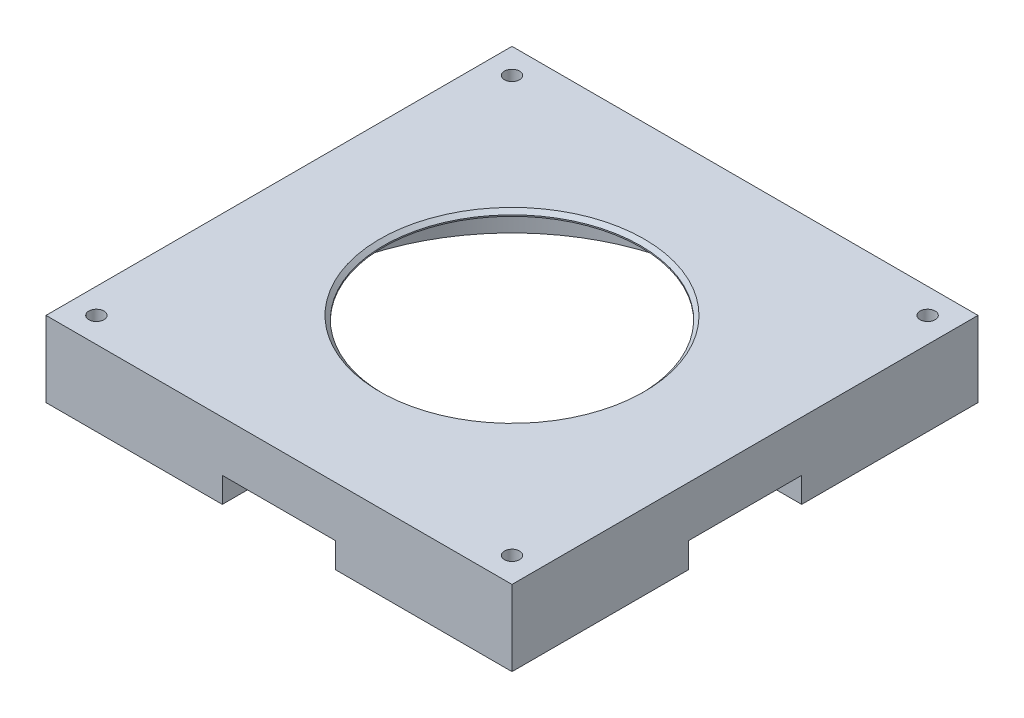
SolidWorks part; units mm, degrees
material "PBT General Purpose"
ref_plane "Front Plane" through (0, 0, 0) normal (0, 0, 1) x (1, 0, 0)
ref_plane "Top Plane" through (0, 0, 0) normal (0, 1, 0) x (1, 0, 0)
ref_plane "Right Plane" through (0, 0, 0) normal (1, 0, 0) x (0, 0, -1)
sketch "Sketch1" plane through (0, 0, 0) normal (0, 0, 1) x (1, 0, 0)
  line L1 (51, -2) -> (82.5, -2)
  line L2 (82.5, -2) -> (82.5, -30)
  line L5 (82.5, -30) -> (85.5, -30)
  line L6 (85.5, -30) -> (85.5, 0)
  line L7 (85.5, 0) -> (51, 0)
  line L8 (51, -2) -> (51, 0)
  line L9 (0, 0) -> (51, 0) construction
  line L10 (0, 0) -> (0, -6.871) construction
  point P2 (65, -8)
  point P3 (64.6623, -8)
  dimension "D1" = 3
  dimension "D3" = 2
  dimension "D5" = 30
  dimension "D6" = 82.5
  dimension "D7" = 51
revolve "Revolve1" add sketch "Sketch1" angle 360 about L10
chamfer "Chamfer1" distance 1.5 angle 45 1 edges at (0, 0, 51)
sketch "Sketch2" plane through (0, -30, 0) normal (0, -1, 0) x (1, 0, 0)
  line L1 (-92.5, -92.5) -> (92.5, -92.5)
  line L2 (-92.5, -92.5) -> (-92.5, 92.5)
  line L3 (-92.5, 92.5) -> (92.5, 92.5)
  line L4 (92.5, -92.5) -> (92.5, 92.5)
  line L5 (-92.5, -92.5) -> (92.5, 92.5) construction
  line L6 (-92.5, 92.5) -> (92.5, -92.5) construction
  line L7 (-82.5, -82.5) -> (82.5, -82.5) construction
  line L8 (-82.5, -82.5) -> (-82.5, 82.5) construction
  line L9 (-82.5, 82.5) -> (82.5, 82.5) construction
  line L10 (82.5, -82.5) -> (82.5, 82.5) construction
  line L11 (-82.5, -82.5) -> (82.5, 82.5) construction
  line L12 (-82.5, 82.5) -> (82.5, -82.5) construction
  circle A0 centre (0, 0) radius 85.5
  circle A1 centre (0, 0) radius 85.5 construction
  circle A6 centre (-82.5, -82.5) radius 3
  circle A7 centre (82.5, -82.5) radius 3
  circle A8 centre (82.5, 82.5) radius 3
  circle A9 centre (-82.5, 82.5) radius 3
  point P16 (81.188, -83.8437)
  point P18 (83.2476, 82.5)
  point P20 (-81.9739, 81.9739)
  dimension "D3" = 6
  dimension "D1" = 185
  dimension "D2" = 165
extrude "Boss-Extrude1" add sketch "Sketch2" against normal up to surface (30 mm away) up to face at (0, 0, -52.5)
sketch "Sketch3" plane through (-92.5, 0, 0) normal (-1, 0, 0) x (0, 0, 1)
  line L0 (92.5, -30) -> (-92.5, -30) construction
  line L1 (-22.5, -30) -> (22.5, -30)
  line L2 (-22.5, -30) -> (-22.5, -20)
  line L3 (-22.5, -20) -> (22.5, -20)
  line L4 (22.5, -30) -> (22.5, -20)
  line L5 (0, 0) -> (0, -20) construction
  line L6 (92.5, 0) -> (92.5, -30) construction
  dimension "D1" = 10
  dimension "D2" = 70
extrude "Cut-Extrude1" cut sketch "Sketch3" against normal through all
sketch "Sketch4" plane through (0, 0, -92.5) normal (0, 0, -1) x (-1, 0, 0)
  line L0 (92.5, -30) -> (-92.5, -30) construction
  line L1 (-22.5, -30) -> (22.5, -30)
  line L2 (-22.5, -30) -> (-22.5, -20)
  line L3 (-22.5, -20) -> (22.5, -20)
  line L4 (22.5, -30) -> (22.5, -20)
  line L5 (0, 0) -> (0, -20) construction
  line L6 (92.5, 0) -> (92.5, -30) construction
  dimension "D1" = 10
  dimension "D2" = 70
extrude "Cut-Extrude2" cut sketch "Sketch4" against normal through all
sketch3d "3DSketch2"
  point P0 (-94.5, 0, 94.5)
